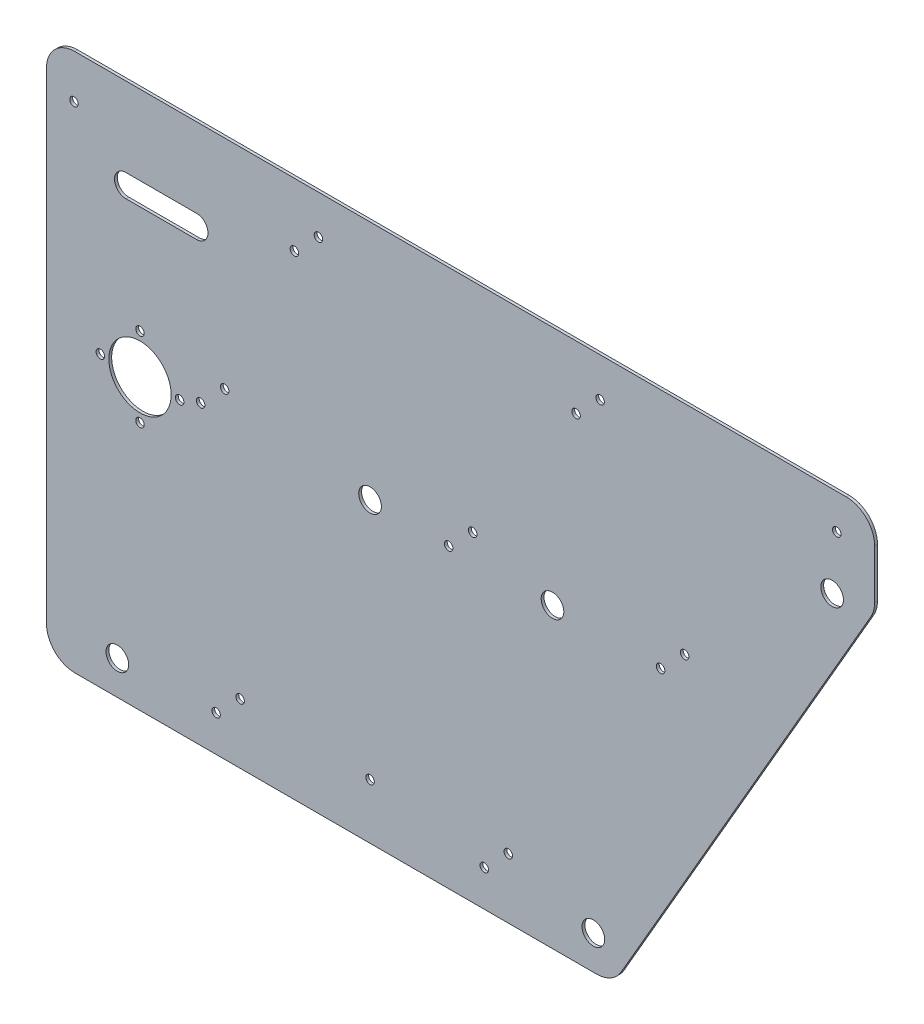
SolidWorks part; units mm, degrees
ref_plane "Front Plane" through (0, 0, 0) normal (0, 0, 1) x (1, 0, 0)
ref_plane "Top Plane" through (0, 0, 0) normal (0, 1, 0) x (1, 0, 0)
ref_plane "Right Plane" through (0, 0, 0) normal (1, 0, 0) x (0, 0, -1)
sketch "Sketch1" plane through (0, 0, 0) normal (0, 0, 1) x (1, 0, 0)
  line L0 (100, 80) -> (192.376, 80)
  line L1 (-100, -80) -> (100, -80)
  line L2 (-100, -80) -> (-100, 80)
  line L3 (-100, 80) -> (100, 80)
  line L4 (100, -80) -> (100, 80)
  line L5 (-100, -80) -> (100, 80) construction
  line L6 (-100, 80) -> (100, -80) construction
  line L7 (192.376, 80) -> (100, -80)
  line L8 (100, 80) -> (100, -80)
  line L10 (-100, 80) -> (192.376, 80)
  line L11 (-100, 80) -> (-100, 110)
  line L12 (-100, 110) -> (192.376, 110)
  line L13 (192.376, 80) -> (192.376, 110)
  point P0 (0, 0)
  dimension "D1" = 160
  dimension "D2" = 200
  dimension "D3" = 30
  dimension "D4" = 30
extrude "Boss-Extrude1" add sketch "Sketch1" along normal blind 1 contours L1 L4 L3 L2 | L7 L0 L4 | L11 L10 L13 L12 region at (0, 0, 0) region at (130.792, 26.6667, 0)
fillet "Fillet1" radius 10 5 edges at (100, -80, 0.5) (-100, -80, 0.5) (192.376, 110, 0.5) (192.376, 80, 0.5) (-100, 110, 0.5)
sketch "Sketch2" plane through (0, 0, 1) normal (0, 0, 1) x (1, 0, 0)
  line L0 (-90, -80) -> (94.2265, -80) construction
  line L1 (191.0363, 77.6795) -> (102.8868, -75) construction
  line L3 (-100, -70) -> (-100, 100) construction
  line L4 (-72, 78) -> (-47, 78) construction
  line L7 (-90, 110) -> (182.376, 110) construction
  line L9 (-72, 82) -> (-47, 82)
  line L10 (-72, 74) -> (-47, 74)
  line L11 (-100, -70) -> (-100, 100) construction
  circle A0 centre (93.0718, -68) radius 4
  circle A1 centre (177.3649, 78) radius 4
  circle A2 centre (-67, 22) radius 11
  circle A3 centre (-75, -68) radius 4
  circle A4 centre (-53, 22) radius 1.5
  circle A5 centre (-67, 36) radius 1.5
  circle A6 centre (-81, 22) radius 1.5
  circle A7 centre (-67, 8) radius 1.5
  circle A11 centre (54.5495, -67.2426) radius 1.5
  circle A12 centre (63.0348, -58.7574) radius 1.5
  circle A13 centre (14.2259, -60.5) radius 1.5
  circle A14 centre (-40.1271, -67.2426) radius 1.5
  circle A15 centre (-31.6419, -58.7574) radius 1.5
  circle A16 centre (-90.2956, 94.5) radius 1.5
  circle A17 centre (-12.4828, 87.7574) radius 1.5
  circle A18 centre (-3.9975, 96.2426) radius 1.5
  circle A19 centre (86.9654, 87.7574) radius 1.5
  circle A20 centre (95.4507, 96.2426) radius 1.5
  circle A21 centre (41.9695, 24.7574) radius 1.5
  circle A22 centre (50.4548, 33.2426) radius 1.5
  circle A23 centre (-45.6014, 24.7574) radius 1.5
  circle A24 centre (-37.1161, 33.2426) radius 1.5
  circle A25 centre (116.8113, 24.7574) radius 1.5
  circle A26 centre (125.2966, 33.2426) radius 1.5
  circle A27 centre (78.6382, 25) radius 4
  circle A28 centre (14.2259, 25) radius 4
  arc A29 (-72, 82) -> (-72, 74) centre (-72, 78) ccw
  arc A30 (-47, 74) -> (-47, 82) centre (-47, 78) ccw
  circle A31 centre (178.9933, 97.6095) radius 1.5
  point P26 (-59.5, 78)
  dimension "D3" = 8
  dimension "D4" = 8
  dimension "D9" = 22
  dimension "D10" = 8
  dimension "D12" = 3
  dimension "D13" = 3
  dimension "D14" = 3
  dimension "D15" = 3
  dimension "D16" = 14
  dimension "D20" = 8
  dimension "D22" = 4
  dimension "D25" = 3
  dimension "D26" = 3
  dimension "D29" = 8
  dimension "D28" = 3
  dimension "D1" = 12
  dimension "D2" = 12
  dimension "D5" = 32
  dimension "D6" = 12
  dimension "D7" = 88
  dimension "D8" = 33
  dimension "D11" = 12
  dimension "D17" = 14
  dimension "D18" = 14
  dimension "D19" = 14
  dimension "D21" = 85
  dimension "D23" = 28
  dimension "D24" = 25
  dimension "D27" = 25
extrude "Cut-Extrude1" cut sketch "Sketch2" against normal blind 3
